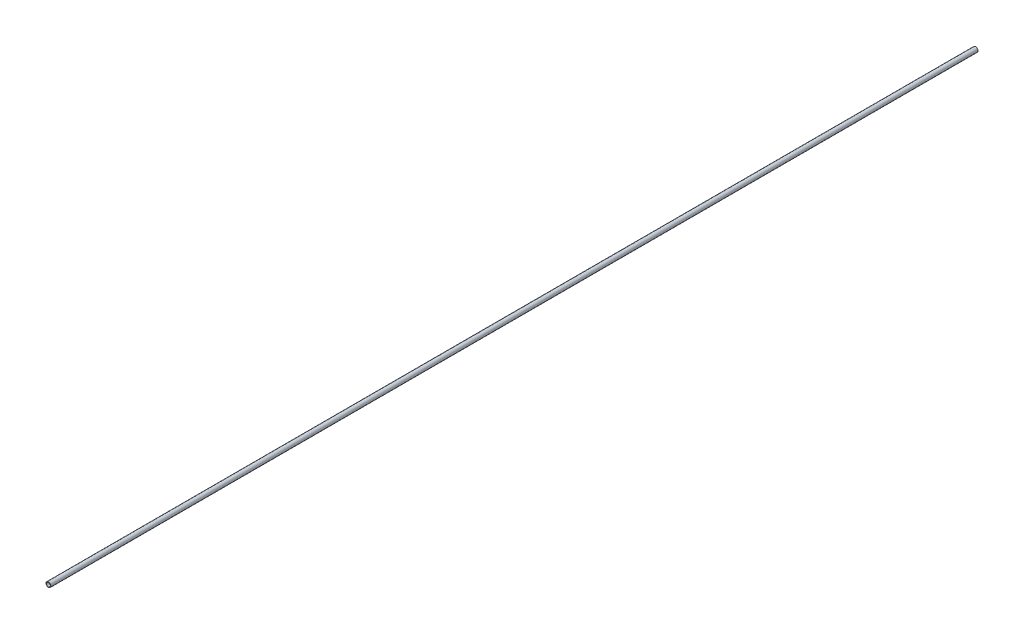
SolidWorks part; units mm, degrees
material "Plain Carbon Steel"
ref_plane "Plane1" through (0, 0, 0) normal (0, 0, 1) x (1, 0, 0)
ref_plane "Plane2" through (0, 0, 0) normal (0, 1, 0) x (1, 0, 0)
ref_plane "Plane3" through (0, 0, 0) normal (1, 0, 0) x (0, 0, -1)
sketch "Sketch1" plane through (0, 0, 0) normal (0, 0, 1) x (1, 0, 0)
  circle A0 centre (0, 0) radius 13.3223
  circle A1 centre (0, 0) radius 16.7005
extrude "BasePipe" add sketch "Sketch1" along normal blind 6426.2
